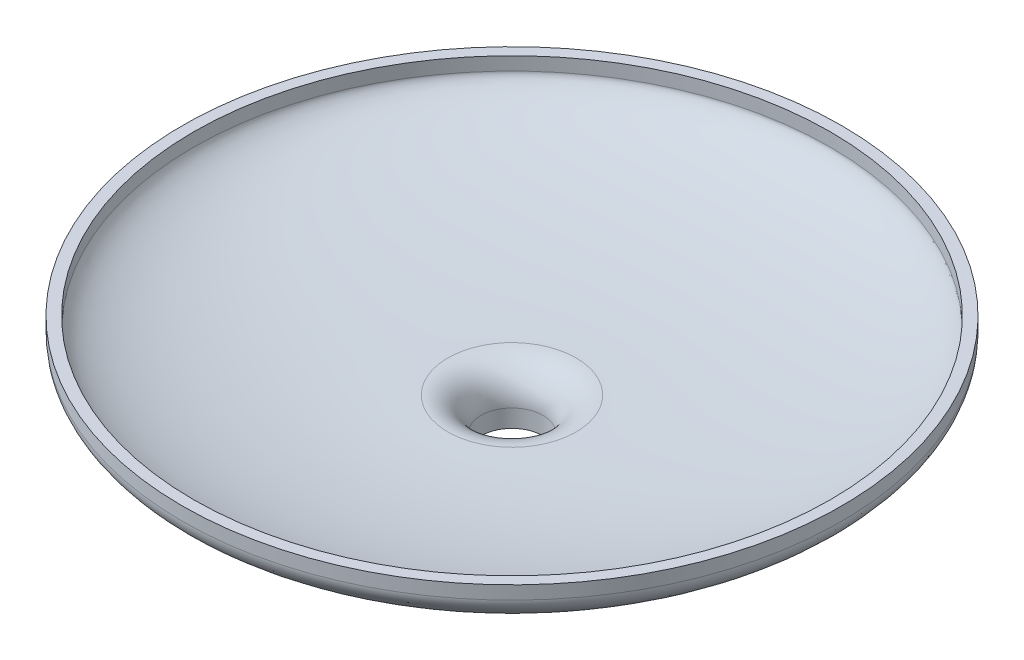
SolidWorks part; units mm, degrees
ref_plane "Front Plane" through (0, 0, 0) normal (0, 0, 1) x (1, 0, 0)
ref_plane "Top Plane" through (0, 0, 0) normal (0, 1, 0) x (1, 0, 0)
ref_plane "Right Plane" through (0, 0, 0) normal (1, 0, 0) x (0, 0, -1)
sketch "Sketch2" plane through (0, 0, 0) normal (0, 0, 1) x (1, 0, 0)
  line L0 (-72, 23) -> (-72, 20)
  line L1 (-74.5, 23) -> (-74.5, 20)
  line L2 (0, 0) -> (0, 18449.246) construction
  line L3 (-9.5, 0) -> (-7, 0) construction
  line L4 (-74.5, 23) -> (-72, 23)
  line L5 (-7, 0) -> (-7, -4)
  line L6 (-7, -4) -> (-9.5, -4)
  line L7 (-9.5, -4) -> (-9.5, 0)
  arc A0 (-9.5, 0) -> (-14.5, 5) centre (-14.5, 0) ccw
  arc A1 (-7, 0) -> (-14.5, 7.5) centre (-14.5, 0) ccw
  ellipse E0 centre (-14.5, 20) end of major axis (45.5, 20) minor radius 15 (-14.5, 5) -> (-74.5, 20) cw
  spline S0 degree 1 poles (-14.5, 7.5) (-72, 20) knots 0 0 1 1 construction
  spline S1 degree 3 poles (-72, 20) (-72, 19.9149) (-71.9847, 19.7557) (-71.8735, 19.3601) (-71.4908, 18.6725) (-70.4317, 17.5934) (-68.1777, 16.0073) (-63.8564, 13.9689) (-56.6052, 11.7568) (-47.6434, 9.9163) (-37.3551, 8.5408) (-28.0235, 7.8331) (-20.3305, 7.5477) (-16.44, 7.5) (-14.5, 7.5) knots 3.141593 3.141593 3.141593 3.141593 3.19068 3.239767 3.337942 3.436117 3.534292 3.730641 3.926991 4.12334 4.31969 4.516039 4.614214 4.712389 4.712389 4.712389 4.712389
  point P10 (0, 0)
  dimension "D2" = 5
  dimension "D1" = 9.5
  dimension "D3" = 15
  dimension "D4" = 60
  dimension "D5" = 3
  dimension "D6" = 2.5
  dimension "D7" = 4
revolve "Revolve1" add sketch "Sketch2" angle 360 about L2
